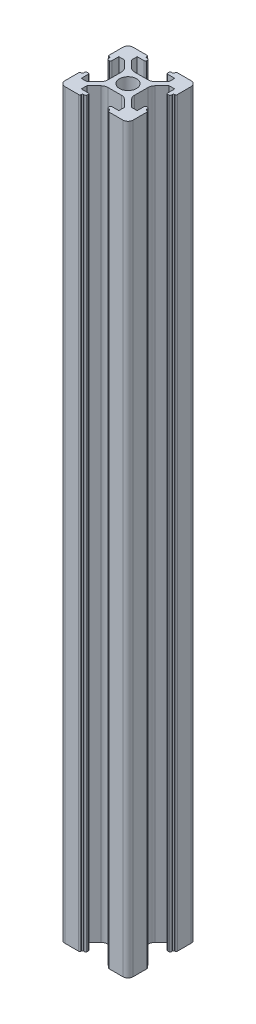
SolidWorks part; units mm, degrees
ref_plane "Front Plane" through (0, 0, 0) normal (0, 0, 1) x (1, 0, 0)
ref_plane "Top Plane" through (0, 0, 0) normal (0, 1, 0) x (1, 0, 0)
ref_plane "Right Plane" through (0, 0, 0) normal (1, 0, 0) x (0, 0, -1)
sketch "Sketch1" plane through (0, 0, 0) normal (0, 1, 0) x (1, 0, 0)
  line L0 (3.4251, 4.4858) -> (5.5, 6.5607)
  line L1 (-10, -10) -> (10, -10) construction
  line L2 (-10, -10) -> (-10, 10) construction
  line L3 (-10, 10) -> (10, 10) construction
  line L4 (10, -10) -> (10, 10) construction
  line L5 (-10, -10) -> (10, 10) construction
  line L6 (-10, 10) -> (10, -10) construction
  line L9 (0, 3.9) -> (2.0109, 3.9)
  line L10 (3.9, 0) -> (3.9, 2.0109)
  line L11 (3.9, 0) -> (3.9, -2.0109)
  line L12 (4.4858, -3.4251) -> (6.5607, -5.5)
  line L13 (4.4858, 3.4251) -> (6.5607, 5.5)
  line L14 (5.5, 8.2) -> (3.1, 8.2)
  line L15 (3.1, 8.2) -> (3.1, 9.24)
  line L16 (5.5, 8.2) -> (5.5, 6.5607)
  line L17 (8.2, 5.5) -> (6.5607, 5.5)
  line L21 (4.1, 10) -> (4.1, 9.24)
  line L22 (8.2, 5.5) -> (8.2, 3.1)
  line L23 (8.2, 3.1) -> (9.24, 3.1)
  line L24 (9.24, 3.1) -> (9.24, 4.1)
  line L25 (10, 4.1) -> (9.24, 4.1)
  line L26 (0, 0) -> (50000, 0) construction
  line L27 (0, 0) -> (0, -50000) construction
  line L28 (4.1, 10) -> (8.5, 10)
  line L29 (10, 8.5) -> (10, 4.1)
  line L30 (4.1, 9.24) -> (3.1, 9.24)
  line L31 (8.2, -5.5) -> (6.5607, -5.5)
  line L32 (8.2, -5.5) -> (8.2, -3.1)
  line L33 (8.2, -3.1) -> (9.24, -3.1)
  line L34 (9.24, -4.1) -> (9.24, -3.1)
  line L35 (10, -4.1) -> (9.24, -4.1)
  line L36 (10, -4.1) -> (10, -8.5)
  line L37 (8.5, -10) -> (4.1, -10)
  line L38 (4.1, -10) -> (4.1, -9.24)
  line L39 (3.1, -9.24) -> (4.1, -9.24)
  line L40 (3.1, -8.2) -> (3.1, -9.24)
  line L41 (5.5, -8.2) -> (3.1, -8.2)
  line L42 (5.5, -8.2) -> (5.5, -6.5607)
  line L43 (3.4251, -4.4858) -> (5.5, -6.5607)
  line L44 (0, -3.9) -> (2.0109, -3.9)
  line L45 (0, -3.9) -> (-2.0109, -3.9)
  line L46 (-3.4251, -4.4858) -> (-5.5, -6.5607)
  line L47 (-5.5, -8.2) -> (-5.5, -6.5607)
  line L48 (-5.5, -8.2) -> (-3.1, -8.2)
  line L49 (-3.1, -8.2) -> (-3.1, -9.24)
  line L50 (-4.1, -9.24) -> (-3.1, -9.24)
  line L51 (-4.1, -10) -> (-4.1, -9.24)
  line L52 (-4.1, -10) -> (-8.5, -10)
  line L53 (-10, -8.5) -> (-10, -4.1)
  line L54 (-10, -4.1) -> (-9.24, -4.1)
  line L55 (-9.24, -3.1) -> (-9.24, -4.1)
  line L56 (-8.2, -3.1) -> (-9.24, -3.1)
  line L57 (-8.2, -5.5) -> (-8.2, -3.1)
  line L58 (-8.2, -5.5) -> (-6.5607, -5.5)
  line L59 (-4.4858, -3.4251) -> (-6.5607, -5.5)
  line L60 (-3.9, 0) -> (-3.9, -2.0109)
  line L61 (-3.9, 0) -> (-3.9, 2.0109)
  line L62 (-4.4858, 3.4251) -> (-6.5607, 5.5)
  line L63 (-8.2, 5.5) -> (-6.5607, 5.5)
  line L64 (-8.2, 5.5) -> (-8.2, 3.1)
  line L65 (-8.2, 3.1) -> (-9.24, 3.1)
  line L66 (-9.24, 4.1) -> (-9.24, 3.1)
  line L67 (-10, 4.1) -> (-9.24, 4.1)
  line L68 (-10, 4.1) -> (-10, 8.5)
  line L69 (-8.5, 10) -> (-4.1, 10)
  line L70 (-4.1, 10) -> (-4.1, 9.24)
  line L71 (-3.1, 9.24) -> (-4.1, 9.24)
  line L72 (-3.1, 8.2) -> (-3.1, 9.24)
  line L73 (-5.5, 8.2) -> (-3.1, 8.2)
  line L74 (-5.5, 8.2) -> (-5.5, 6.5607)
  line L75 (-3.4251, 4.4858) -> (-5.5, 6.5607)
  line L76 (0, 3.9) -> (-2.0109, 3.9)
  arc A1 (3.9, 2.0109) -> (4.4858, 3.4251) centre (5.9, 2.0109) cw
  arc A2 (3.4251, 4.4858) -> (2.0109, 3.9) centre (2.0109, 5.9) cw
  arc A3 (10, 8.5) -> (8.5, 10) centre (8.5, 8.5) ccw
  arc A4 (2.5, 0) -> (0, 2.5) centre (0, 0) ccw
  arc A5 (0, -2.5) -> (2.5, 0) centre (0, 0) ccw
  arc A6 (4.4858, -3.4251) -> (3.9, -2.0109) centre (5.9, -2.0109) cw
  arc A7 (8.5, -10) -> (10, -8.5) centre (8.5, -8.5) ccw
  arc A8 (2.0109, -3.9) -> (3.4251, -4.4858) centre (2.0109, -5.9) cw
  arc A9 (-2.5, 0) -> (0, -2.5) centre (0, 0) ccw
  arc A10 (-3.4251, -4.4858) -> (-2.0109, -3.9) centre (-2.0109, -5.9) cw
  arc A11 (-10, -8.5) -> (-8.5, -10) centre (-8.5, -8.5) ccw
  arc A12 (-3.9, -2.0109) -> (-4.4858, -3.4251) centre (-5.9, -2.0109) cw
  arc A13 (0, 2.5) -> (-2.5, 0) centre (0, 0) ccw
  arc A14 (-4.4858, 3.4251) -> (-3.9, 2.0109) centre (-5.9, 2.0109) cw
  arc A15 (-8.5, 10) -> (-10, 8.5) centre (-8.5, 8.5) ccw
  arc A16 (-2.0109, 3.9) -> (-3.4251, 4.4858) centre (-2.0109, 5.9) cw
  point P0 (0, 0)
  point P30 (3.1, 10)
  point P115 (0, 0)
  dimension "D2" = 2.5
  dimension "D3" = 2
  dimension "D12" = 1.5
  dimension "D1" = 20
  dimension "D4" = 1.5
  dimension "D5" = 1.8
  dimension "D6" = 5.5
  dimension "D7" = 0.76
  dimension "D8" = 3.1
  dimension "D9" = 1
  dimension "D10" = 3.9
  dimension "D11" = 3.9
  dimension "D13" = 4
extrude "Boss-Extrude1" add sketch "Sketch1" along normal blind 217.56 contours L76 A16 L75 L74 L73 L72 L71 L70 L69 A15 L68 L67 L66 L65 L64 L63 L62 A14 L61 L60 A12 L59 L58 L57 L56 L55 L54 L53 A11 L52 L51 L50 L49 L48 L47 L46 A10 L45 L44 A8 L43 L42 L41 L40 L39 L38 L37 A7 L36 L35 L34 region at (4.6626, 0, -5.3232)
fillet "Fillet1" radius 0.35 33 edges at (-4.1, 108.78, -10) (-4.1, 108.78, -9.24) (-3.1, 108.78, -9.24) (-3.1, 108.78, -8.2) (-9.24, 108.78, -4.1) (-10, 108.78, -4.1) (-9.24, 108.78, -3.1) (-8.2, 108.78, -3.1) (-10, 108.78, 4.1) (-9.24, 108.78, 4.1) (-9.24, 108.78, 3.1) (-8.2, 108.78, 3.1) (-4.1, 108.78, 10) (-4.1, 108.78, 9.24) (-3.1, 108.78, 9.24) (-3.1, 108.78, 8.2) (4.1, 108.78, 10) (4.1, 108.78, 9.24) (3.1, 108.78, 9.24) (3.1, 108.78, 8.2) (10, 108.78, 4.1) (9.24, 108.78, 4.1) (9.24, 108.78, 3.1) (8.2, 108.78, 3.1) (10, 108.78, -4.1) (9.24, 108.78, -4.1) (9.24, 108.78, -3.1) (8.2, 108.78, -3.1) (3.1, 108.78, -8.2) (4.1, 108.78, -10) (5.5, 108.78, -6.5607) (3.1, 108.78, -9.24) (4.1, 108.78, -9.24)
